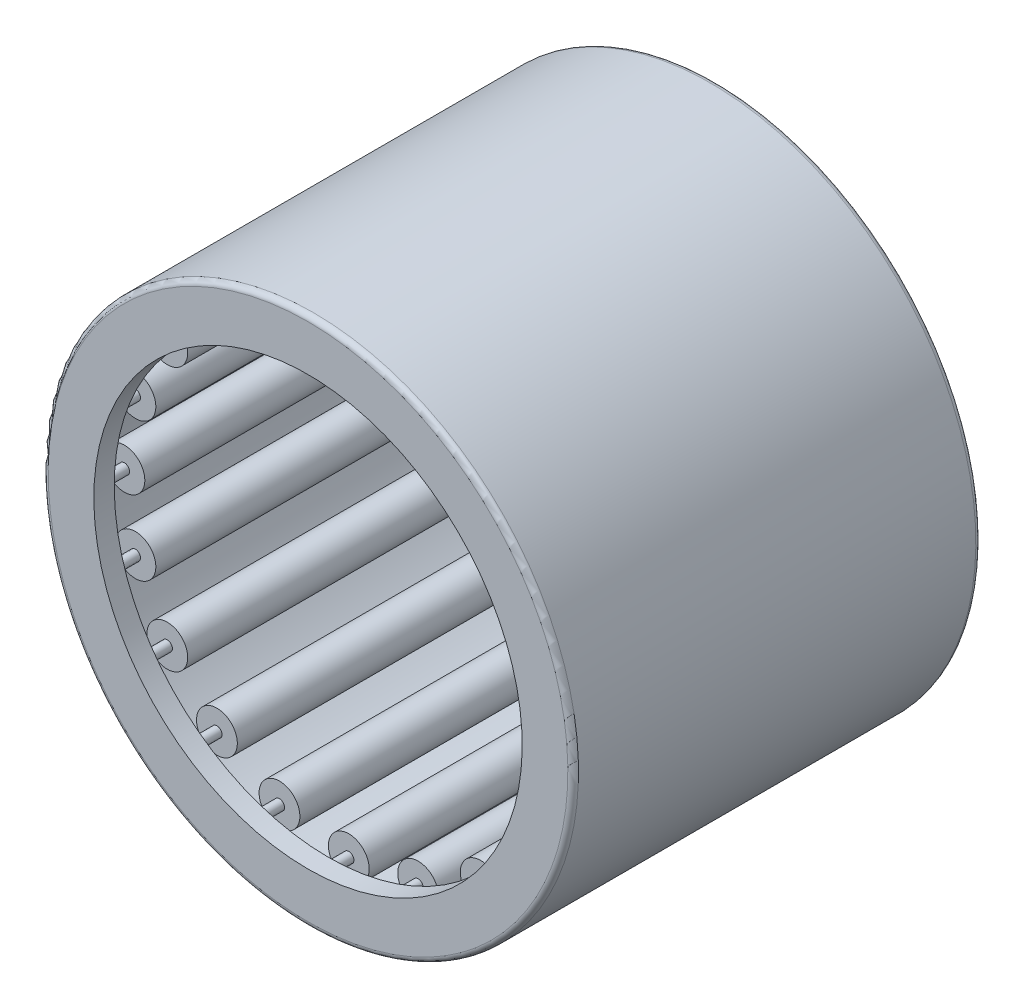
SolidWorks part; units mm, degrees
material "Alloy Steel"
ref_plane "Front Plane" through (0, 0, 0) normal (0, 0, 1) x (1, 0, 0)
ref_plane "Top Plane" through (0, 0, 0) normal (0, 1, 0) x (1, 0, 0)
ref_plane "Right Plane" through (0, 0, 0) normal (1, 0, 0) x (0, 0, -1)
sketch "Sketch1" plane through (0, 0, 0) normal (1, 0, 0) x (0, 0, -1)
  line L0 (-10, 0) -> (10, 0) construction
  line L1 (0, 0) -> (0, 13) construction
  line L2 (-10, 0) -> (-10, 13) construction
  line L3 (-10, 13) -> (10, 13)
  line L4 (10, 13) -> (10, 0) construction
  line L5 (10, 0) -> (9, 0) construction
  line L6 (9, 0) -> (9, 12) construction
  line L7 (9, 12) -> (-9, 12)
  line L8 (-9, 12) -> (-9, 0) construction
  line L9 (-9, 0) -> (-10, 0) construction
  line L10 (-10, 13) -> (-10, 10.5)
  line L11 (-10, 10.5) -> (-9, 10.5)
  line L12 (-9, 10.5) -> (-9, 12)
  line L13 (9, 13) -> (9, 12) construction
  line L14 (9, 12) -> (9, 10.5)
  line L15 (9, 10.5) -> (10, 10.5)
  line L16 (10, 10.5) -> (10, 13)
  line L17 (9, 12) -> (9, 11) construction
  line L18 (9, 11) -> (9, 10) construction
  line L19 (9, -12) -> (9, -11) construction
  line L20 (9, -13) -> (9, -12) construction
  line L21 (10, -10.5) -> (10, -13) construction
  line L22 (9, -10.5) -> (10, -10.5) construction
  line L23 (9, -12) -> (9, -10.5) construction
  line L24 (-9, -10.5) -> (-9, -12) construction
  line L25 (-10, -10.5) -> (-9, -10.5) construction
  line L26 (-10, -13) -> (-10, -10.5) construction
  line L27 (9, -12) -> (-9, -12) construction
  line L28 (-10, -13) -> (10, -13) construction
  point P4 (0, 10)
  dimension "C | Width" = 20
  dimension "Fw | ID" = 20
  dimension "D | OD" = 26
sketch "Sketch7" plane through (0, 0, 0) normal (1, 0, 0) x (0, 0, -1)
  line L0 (-10, 13) -> (-10, 10.5) construction
  line L1 (-10, 10.5) -> (-9, 10.5) construction
  line L2 (-9, 10.5) -> (-9, 12) construction
  line L3 (9, 12) -> (-9, 12) construction
  line L4 (9, 12) -> (9, 10.5) construction
  line L5 (9, 10.5) -> (10, 10.5) construction
  line L6 (10, 10.5) -> (10, 13) construction
  line L8 (-10, 13) -> (10, 13) construction
  line L9 (-10, 13) -> (-10, 10.5)
  line L10 (-10, 10.5) -> (-9, 10.5)
  line L13 (-9, 10.5) -> (-9, 12)
  line L16 (9, 12) -> (-9, 12)
  line L17 (9, 12) -> (9, 10.5)
  line L18 (9, 10.5) -> (10, 10.5)
  line L19 (10, 10.5) -> (10, 13)
  line L20 (-10, 13) -> (10, 13)
revolve "Revolve1" add sketch "Sketch7" angle 360 about L0
sketch "Sketch2" plane through (0, 0, 0) normal (1, 0, 0) x (0, 0, -1)
  line L0 (-10, 10.5) -> (-9, 10.5) construction
  line L1 (-8, 11) -> (8, 11) construction
  line L2 (-8, 11) -> (-8, 12) construction
  line L3 (-8, 12) -> (8, 12)
  line L4 (8, 11) -> (8, 12) construction
  line L5 (9, 10.5) -> (10, 10.5) construction
  line L6 (-9, 11) -> (-8, 11) construction
  line L7 (8, 11) -> (9, 11) construction
  line L8 (10, 13) -> (10, 0) construction
  line L9 (-8, 11.25) -> (-8, 10.75) construction
  line L10 (-9, 11) -> (-9, 10.5) construction
  line L11 (-8, 12) -> (-8, 11.25)
  line L12 (8, 12) -> (8, 11.25)
  line L13 (8, 11.25) -> (-8, 11.25)
  line L14 (0, 12) -> (0, 10) construction
  line L16 (-8, 10.75) -> (-9, 10.75) construction
  line L17 (0, 0) -> (10, 0) construction
  line L18 (-8, -10.75) -> (-9, -10.75) construction
  line L19 (0, -12) -> (0, -10) construction
  line L20 (-9, -11) -> (-9, -10.5) construction
  line L21 (-8, -11.25) -> (-8, -10.75) construction
  line L22 (8, -11) -> (9, -11) construction
  line L23 (-9, -11) -> (-8, -11) construction
  line L24 (8, -11) -> (8, -12) construction
  line L25 (-8, -11) -> (-8, -12) construction
  line L26 (-8, -11) -> (8, -11) construction
  line L27 (8, -11.25) -> (-8, -11.25) construction
  line L28 (8, -12) -> (8, -11.25) construction
  line L29 (-8, -12) -> (-8, -11.25) construction
  line L30 (-8, -12) -> (8, -12) construction
  line L33 (9, 12) -> (-9, 12) construction
  line L34 (9, 12) -> (9, 10.5) construction
  line L35 (-9, 10.5) -> (-9, 12) construction
  line L36 (0, 0) -> (0, 13) construction
  point P16 (0, 11)
revolve "Revolve2" add sketch "Sketch2" angle 360 about L1
sketch "Sketch3" plane through (0, 0, 0) normal (1, 0, 0) x (0, 0, -1)
  line L1 (-9, 11) -> (9, 11)
  line L2 (-9, 11) -> (-9, 11.25)
  line L3 (-9, 11.25) -> (9, 11.25)
  line L4 (9, 11) -> (9, 11.25)
  line L5 (0, 0) -> (10, 0) construction
  line L7 (9, -11) -> (9, -11.25) construction
  line L8 (-9, -11.25) -> (9, -11.25) construction
  line L9 (-9, -11) -> (-9, -11.25) construction
  line L10 (-9, -11) -> (9, -11) construction
  line L11 (9, 12) -> (9, 10.5) construction
  line L12 (10, 13) -> (10, 0) construction
revolve "Revolve3" add sketch "Sketch3" angle 360 about L1
ref_axis "Axis1" through (0, 10.5, 10) along (0, 1, 0)
pattern_circular "CirPattern1" count 20 every 18 about axis through (0, 0, 10) along (0, 0, -1) of bodies 166 167
fillet "Fillet1" radius 0.26 2 edges at (0, -13, -10) (0, -13, 10)
sketch "Front View" plane through (0, 0, 0) normal (0, 0, 1) x (1, 0, 0)
  circle A0 centre (0, 0) radius 10 construction
  circle A1 centre (0, 0) radius 13 construction
  dimension "ID" = 20
  dimension "OD" = 26
sketch "Right View" plane through (0, 0, 0) normal (1, 0, 0) x (0, 0, -1)
  line L0 (-10, 13) -> (10, 13) construction
  line L1 (-10, 13) -> (10, 13) construction
  line L2 (0, 0) -> (0, 13) construction
  point P4 (0, 13)
  dimension "Width" = 20
equation "\"Rollers@CirPattern1\"  = \"OD@Sketch1\"*.75"
equation "\"D1@Fillet1\" = \"D | OD@Sketch1\" * .01"
equation "\"Angle@CirPattern1\"=360 / \"Rollers@CirPattern1\""
equation "\"ID@Front View\" = \"Fw | ID@Sketch1\""
equation "\"OD@Front View\" = \"D | OD@Sketch1\""
equation "\"Width@Right View\" = \"C | Width@Sketch1\""
